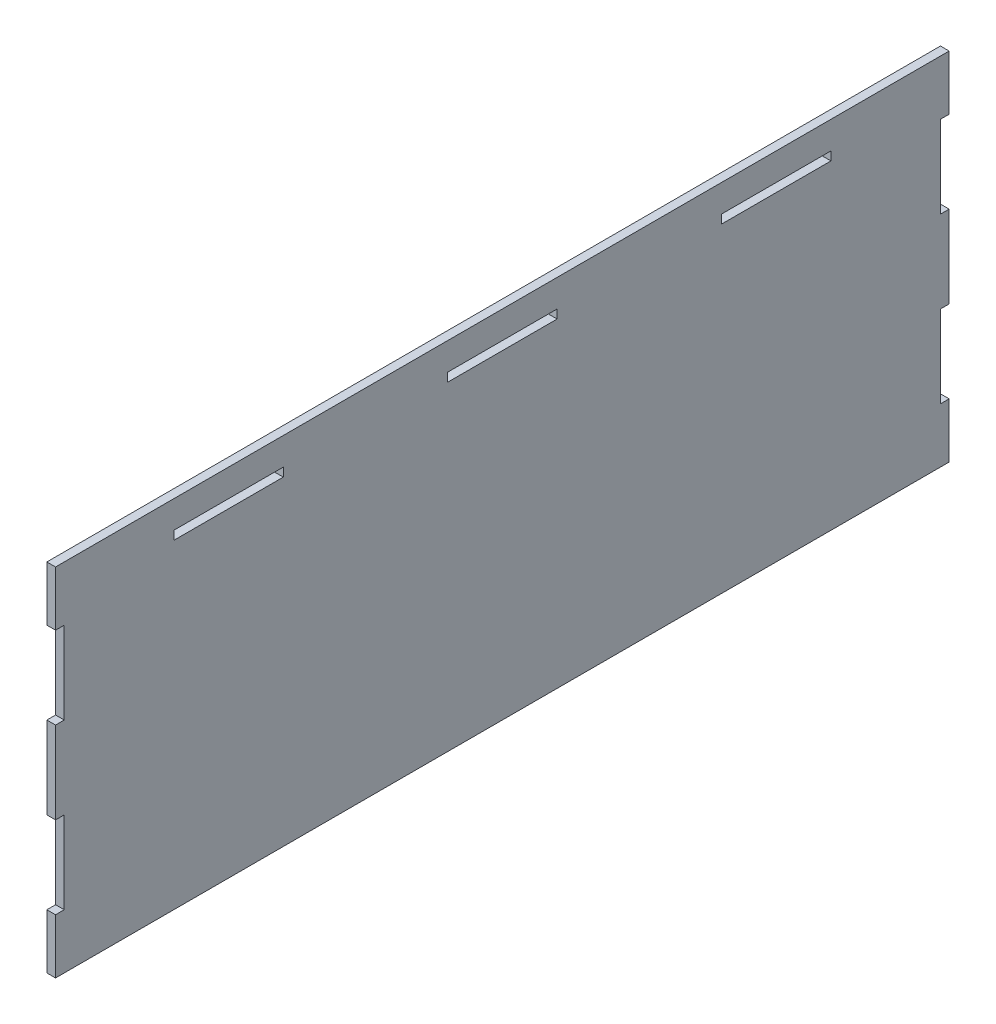
SolidWorks part; units mm, degrees
ref_plane "前视" through (0, 0, 0) normal (0, 0, 1) x (1, 0, 0)
ref_plane "上视" through (0, 0, 0) normal (0, 1, 0) x (1, 0, 0)
ref_plane "右视" through (0, 0, 0) normal (1, 0, 0) x (0, 0, -1)
sketch "Sketch1" plane through (0, 0, 0) normal (1, 0, 0) x (0, 0, -1)
  line L1 (0, 0) -> (326.35, 0)
  line L2 (0, 0) -> (0, -130)
  line L3 (0, -130) -> (326.35, -130)
  line L4 (326.35, 0) -> (326.35, -130)
  dimension "D1" = 326.35
  dimension "D2" = 130
extrude "Boss-Extrude1" add sketch "Sketch1" along normal blind 3.175
ref_axis "Axis1" through (3.175, 0, -163.175) along (0, 1, 0)
sketch "Sketch2" plane through (3.175, 0, 0) normal (1, 0, 0) x (0, 0, -1)
  line L0 (0, -130) -> (326.35, -130) construction
  line L1 (43.175, -10) -> (83.175, -10)
  line L2 (43.175, -10) -> (43.175, -13.175)
  line L3 (43.175, -13.175) -> (83.175, -13.175)
  line L4 (83.175, -10) -> (83.175, -13.175)
  line L5 (0, 0) -> (0, -130) construction
  line L6 (326.35, -130) -> (326.35, 0) construction
  line L7 (143.175, -10) -> (183.175, -10)
  line L8 (143.175, -10) -> (143.175, -13.175)
  line L9 (143.175, -13.175) -> (183.175, -13.175)
  line L10 (183.175, -10) -> (183.175, -13.175)
  line L11 (243.175, -10) -> (283.175, -10)
  line L12 (243.175, -10) -> (243.175, -13.175)
  line L13 (243.175, -13.175) -> (283.175, -13.175)
  line L14 (283.175, -10) -> (283.175, -13.175)
  line L15 (326.35, -20) -> (323.175, -20)
  line L16 (326.35, -20) -> (326.35, -50)
  line L17 (326.35, -50) -> (323.175, -50)
  line L18 (323.175, -20) -> (323.175, -50)
  line L19 (326.35, 0) -> (0, 0) construction
  line L21 (326.35, -80) -> (323.175, -80)
  line L22 (326.35, -80) -> (326.35, -110)
  line L23 (326.35, -110) -> (323.175, -110)
  line L24 (323.175, -80) -> (323.175, -110)
  line L25 (0, -20) -> (3.175, -20)
  line L26 (0, -20) -> (0, -50)
  line L27 (0, -50) -> (3.175, -50)
  line L28 (3.175, -20) -> (3.175, -50)
  line L29 (0, -80) -> (3.175, -80)
  line L30 (0, -80) -> (0, -110)
  line L31 (0, -110) -> (3.175, -110)
  line L32 (3.175, -80) -> (3.175, -110)
  dimension "D1" = 120
  dimension "D2" = 3.175
  dimension "D3" = 43.175
  dimension "D4" = 40
  dimension "D5" = 60
  dimension "D6" = 40
  dimension "D7" = 40
  dimension "D8" = 60
  dimension "D9" = 20
  dimension "D10" = 3.175
  dimension "D11" = 30
  dimension "D12" = 30
  dimension "D13" = 30
  dimension "D14" = 20
  dimension "D15" = 30
  dimension "D16" = 3.175
  dimension "D17" = 30
  dimension "D18" = 30
  dimension "D19" = 3.175
  dimension "D20" = 10
extrude "Cut-Extrude1" cut sketch "Sketch2" against normal blind 10
